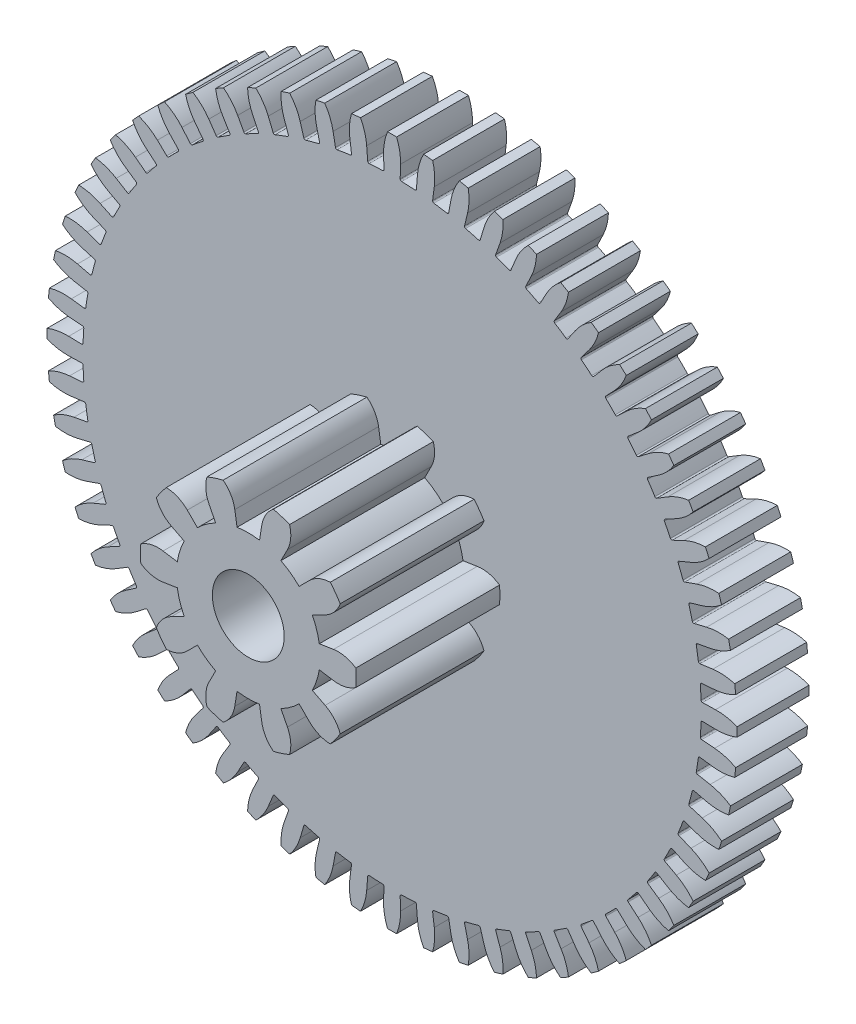
SolidWorks part; units mm, degrees
ref_plane "Front Plane" through (0, 0, 0) normal (0, 0, 1) x (1, 0, 0)
ref_plane "Top Plane" through (0, 0, 0) normal (0, 1, 0) x (1, 0, 0)
ref_plane "Right Plane" through (0, 0, 0) normal (1, 0, 0) x (0, 0, -1)
sketch "Sketch1" plane through (0, 0, 0) normal (0, 0, 1) x (1, 0, 0)
  line L0 (0, 0) -> (6.94, 0) construction
  line L1 (0, 0) -> (4.2941, 0.225) construction
  line L2 (0, 0) -> (5.3526, 0.1402) construction
  line L3 (0, 0) -> (5.9482, 0.0779) construction
  line L4 (4.2985, 0.1126) -> (4.4985, 0.1178)
  line L5 (0, 0) -> (4.2941, 0.225)
  line L6 (4.2985, -0.1126) -> (4.4985, -0.1178)
  line L7 (0, 0) -> (4.2941, -0.225) construction
  line L8 (0, 0) -> (4.2941, -0.225)
  arc A0 (4.8, 0) -> (4.7984, 0.1256) centre (0, 0) ccw construction
  circle A1 centre (0, 0) radius 4.5 construction
  arc A2 (4.2985, 0.1126) -> (4.3, 0) centre (0, 0) ccw construction
  arc A3 (4.4985, 0.1178) -> (4.7996, 0.0628) centre (4.518, -0.6276) cw
  arc A4 (4.7996, 0.0628) -> (4.7996, -0.0628) centre (0, 0) cw
  arc A5 (4.2941, 0.225) -> (4.2985, 0.1126) centre (0, 0) cw
  arc A6 (4.4985, -0.1178) -> (4.7996, -0.0628) centre (4.518, 0.6276) ccw
  arc A7 (4.2941, -0.225) -> (4.2985, -0.1126) centre (0, 0) ccw
  circle A8 centre (0, 0) radius 4.8 construction
  dimension "D1" = 9.6
  dimension "D2" = 9
  dimension "D3" = 0.5
  dimension "D7" = 4.3
  dimension "D4" = 3
  dimension "D5" = 1.5
  dimension "D6" = 0.75
extrude "Boss-Extrude1" add sketch "Sketch1" along normal blind 1 contours L8 A7 L6 A6 A4 A3 L4 A5 L5 region at (3.0311, 0, 0)
fillet "Fillet1" radius 0.02 2 edges at (4.2985, -0.1126, 0.5) (4.2985, 0.1126, 0.5)
pattern_circular "CirPattern1" count 60 over 360 about axis through (0, 0, 1) along (0, 0, -1) of "Fillet1", "Boss-Extrude1"
ref_plane "Plane1" through (4.2606, -0.581, 1) normal (0.1351, 0.9908, 0) x (0.9908, -0.1351, 0)
sketch "Sketch4" plane through (0, 0, 1) normal (0, 0, 1) x (1, 0, 0)
  circle A0 centre (0, 0) radius 0.5
sketch "Sketch5" plane through (0, 0, 1) normal (0, 0, 1) x (1, 0, 0)
  line L4 (0.9877, 0.1564) -> (1.1852, 0.1877)
  line L5 (0.9877, -0.1564) -> (1.1852, -0.1877)
  line L6 (0.891, -0.454) -> (1.0692, -0.5448)
  line L7 (0.7071, -0.7071) -> (0.8485, -0.8485)
  line L8 (0.454, -0.891) -> (0.5448, -1.0692)
  line L9 (0.1564, -0.9877) -> (0.1877, -1.1852)
  line L10 (-0.1564, -0.9877) -> (-0.1877, -1.1852)
  line L11 (-0.454, -0.891) -> (-0.5448, -1.0692)
  line L12 (-0.7071, -0.7071) -> (-0.8485, -0.8485)
  line L13 (-0.891, -0.454) -> (-1.0692, -0.5448)
  line L14 (-0.9877, -0.1564) -> (-1.1852, -0.1877)
  line L15 (-0.9877, 0.1564) -> (-1.1852, 0.1877)
  line L16 (-0.891, 0.454) -> (-1.0692, 0.5448)
  line L17 (-0.7071, 0.7071) -> (-0.8485, 0.8485)
  line L18 (-0.454, 0.891) -> (-0.5448, 1.0692)
  line L19 (-0.1564, 0.9877) -> (-0.1877, 1.1852)
  line L20 (0.1564, 0.9877) -> (0.1877, 1.1852)
  line L21 (0.454, 0.891) -> (0.5448, 1.0692)
  line L22 (0.7071, 0.7071) -> (0.8485, 0.8485)
  line L23 (0.891, 0.454) -> (1.0692, 0.5448)
  arc A3 (1.1852, 0.1877) -> (1.4954, 0.1177) centre (1.2524, -0.2365) cw
  arc A4 (1.4954, 0.1177) -> (1.4954, -0.1177) centre (0, 0) cw
  arc A5 (0.9511, 0.309) -> (0.9877, 0.1564) centre (0, 0) cw
  arc A6 (1.1852, -0.1877) -> (1.4954, -0.1177) centre (1.2524, 0.2365) ccw
  arc A7 (0.9511, -0.309) -> (0.9877, -0.1564) centre (0, 0) ccw
  arc A8 (0.9511, -0.309) -> (0.891, -0.454) centre (0, 0) cw
  arc A9 (1.0692, -0.5448) -> (1.279, -0.7837) centre (0.8742, -0.9275) cw
  arc A10 (1.279, -0.7837) -> (1.1406, -0.9742) centre (0, 0) cw
  arc A11 (0.8485, -0.8485) -> (1.1406, -0.9742) centre (1.1522, -0.5448) ccw
  arc A12 (0.5878, -0.809) -> (0.7071, -0.7071) centre (0, 0) ccw
  arc A13 (0.5878, -0.809) -> (0.454, -0.891) centre (0, 0) cw
  arc A14 (0.5448, -1.0692) -> (0.574, -1.3858) centre (0.1621, -1.2642) cw
  arc A15 (0.574, -1.3858) -> (0.3502, -1.4586) centre (0, 0) cw
  arc A16 (0.1877, -1.1852) -> (0.3502, -1.4586) centre (0.6119, -1.118) ccw
  arc A17 (0, -1) -> (0.1564, -0.9877) centre (0, 0) ccw
  arc A18 (0, -1) -> (-0.1564, -0.9877) centre (0, 0) cw
  arc A19 (-0.1877, -1.1852) -> (-0.3502, -1.4586) centre (-0.6119, -1.118) cw
  arc A20 (-0.3502, -1.4586) -> (-0.574, -1.3858) centre (0, 0) cw
  arc A21 (-0.5448, -1.0692) -> (-0.574, -1.3858) centre (-0.1621, -1.2642) ccw
  arc A22 (-0.5878, -0.809) -> (-0.454, -0.891) centre (0, 0) ccw
  arc A23 (-0.5878, -0.809) -> (-0.7071, -0.7071) centre (0, 0) cw
  arc A24 (-0.8485, -0.8485) -> (-1.1406, -0.9742) centre (-1.1522, -0.5448) cw
  arc A25 (-1.1406, -0.9742) -> (-1.279, -0.7837) centre (0, 0) cw
  arc A26 (-1.0692, -0.5448) -> (-1.279, -0.7837) centre (-0.8742, -0.9275) ccw
  arc A27 (-0.9511, -0.309) -> (-0.891, -0.454) centre (0, 0) ccw
  arc A28 (-0.9511, -0.309) -> (-0.9877, -0.1564) centre (0, 0) cw
  arc A29 (-1.1852, -0.1877) -> (-1.4954, -0.1177) centre (-1.2524, 0.2365) cw
  arc A30 (-1.4954, -0.1177) -> (-1.4954, 0.1177) centre (0, 0) cw
  arc A31 (-1.1852, 0.1877) -> (-1.4954, 0.1177) centre (-1.2524, -0.2365) ccw
  arc A32 (-0.9511, 0.309) -> (-0.9877, 0.1564) centre (0, 0) ccw
  arc A33 (-0.9511, 0.309) -> (-0.891, 0.454) centre (0, 0) cw
  arc A34 (-1.0692, 0.5448) -> (-1.279, 0.7837) centre (-0.8742, 0.9275) cw
  arc A35 (-1.279, 0.7837) -> (-1.1406, 0.9742) centre (0, 0) cw
  arc A36 (-0.8485, 0.8485) -> (-1.1406, 0.9742) centre (-1.1522, 0.5448) ccw
  arc A37 (-0.5878, 0.809) -> (-0.7071, 0.7071) centre (0, 0) ccw
  arc A38 (-0.5878, 0.809) -> (-0.454, 0.891) centre (0, 0) cw
  arc A39 (-0.5448, 1.0692) -> (-0.574, 1.3858) centre (-0.1621, 1.2642) cw
  arc A40 (-0.574, 1.3858) -> (-0.3502, 1.4586) centre (0, 0) cw
  arc A41 (-0.1877, 1.1852) -> (-0.3502, 1.4586) centre (-0.6119, 1.118) ccw
  arc A42 (0, 1) -> (-0.1564, 0.9877) centre (0, 0) ccw
  arc A43 (0, 1) -> (0.1564, 0.9877) centre (0, 0) cw
  arc A44 (0.1877, 1.1852) -> (0.3502, 1.4586) centre (0.6119, 1.118) cw
  arc A45 (0.3502, 1.4586) -> (0.574, 1.3858) centre (0, 0) cw
  arc A46 (0.5448, 1.0692) -> (0.574, 1.3858) centre (0.1621, 1.2642) ccw
  arc A47 (0.5878, 0.809) -> (0.454, 0.891) centre (0, 0) ccw
  arc A48 (0.5878, 0.809) -> (0.7071, 0.7071) centre (0, 0) cw
  arc A49 (0.8485, 0.8485) -> (1.1406, 0.9742) centre (1.1522, 0.5448) cw
  arc A50 (1.1406, 0.9742) -> (1.279, 0.7837) centre (0, 0) cw
  arc A51 (1.0692, 0.5448) -> (1.279, 0.7837) centre (0.8742, 0.9275) ccw
  arc A52 (0.9511, 0.309) -> (0.891, 0.454) centre (0, 0) ccw
  circle A53 centre (0, 0) radius 1.5 construction
  circle A54 centre (0, 0) radius 1 construction
  circle A55 centre (0, 0) radius 1.2 construction
  point P2 (0, 0)
  point P113 (0, 0)
  dimension "D1" = 3
  dimension "D2" = 2.4
  dimension "D3" = 1
  dimension "D4" = 0.5
  dimension "D7" = 10
extrude "Boss-Extrude2" add sketch "Sketch5" along normal blind 2
extrude "Cut-Extrude1" cut sketch "Sketch4" against normal blind 1 and the other way blind 2
